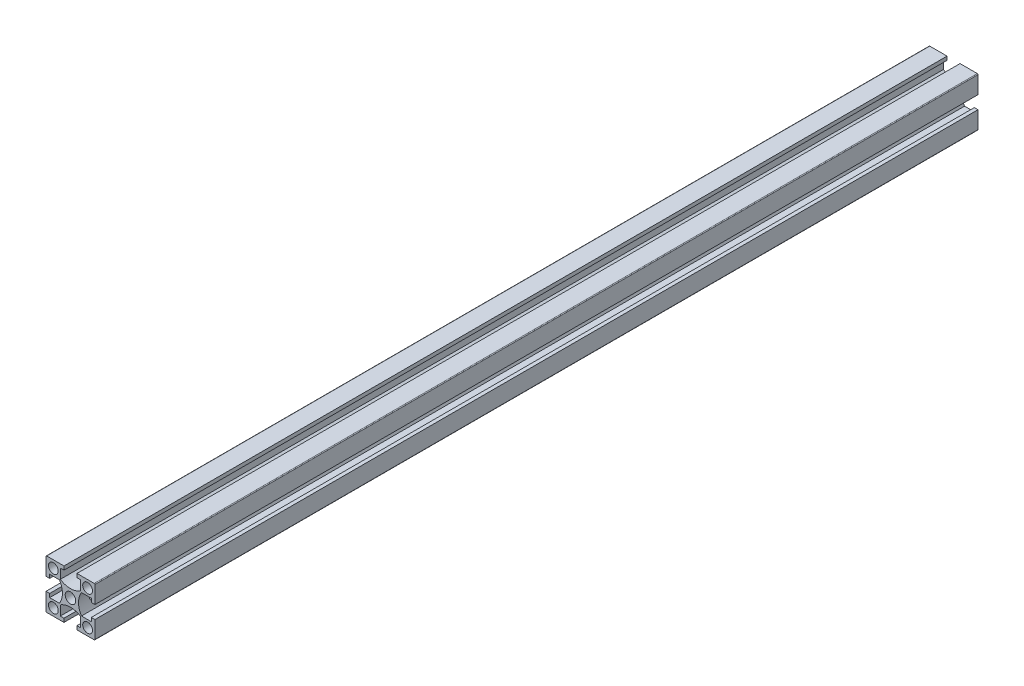
SolidWorks part; units mm, degrees
material "3.0255 (EN-AW 1350A)"
ref_plane "정면" through (0, 0, 0) normal (0, 0, 1) x (1, 0, 0)
ref_plane "윗면" through (0, 0, 0) normal (0, 1, 0) x (1, 0, 0)
ref_plane "우측면" through (0, 0, 0) normal (1, 0, 0) x (0, 0, -1)
sketch "스케치1" plane through (0, 0, 0) normal (0, 0, 1) x (1, 0, 0)
  line L0 (0, 32.0265) -> (0, -31.6588) construction
  line L1 (-10, 10) -> (-10, -10)
  line L2 (-10, 10) -> (10, 10)
  line L3 (-10, 2.65) -> (-8.5, 2.65)
  line L4 (13.6618, 0) -> (-11.6993, 0) construction
  line L5 (-8.5, 2.65) -> (-8.5, 4.15)
  line L6 (-8.5, 4.15) -> (-4.5032, 4.15)
  line L7 (-10, -2.65) -> (-8.5, -2.65)
  line L8 (-8.5, -2.65) -> (-8.5, -4.15)
  line L9 (-8.5, -4.15) -> (-4.5032, -4.15)
  line L10 (-10, -10) -> (10, -10)
  line L11 (10, 10) -> (10, -10)
  circle A0 centre (-7, 7) radius 2
  circle A1 centre (-7, -7) radius 2
  arc A2 (-4.5032, 4.15) -> (-4.5032, -4.15) centre (-11.0587, 0) cw
  circle A3 centre (0, 0) radius 2.15
  circle A4 centre (7, 7) radius 2
  circle A5 centre (7, -7) radius 2
  point P21 (-10, 0)
  point P23 (-3.3, 0)
  point P31 (0, -10)
  point P32 (0, 10)
  dimension "D3" = 4
  dimension "D9" = 6.7
  dimension "D10" = 4.3
  dimension "D11" = 7.7587
  dimension "D1" = 20
  dimension "D2" = 20
  dimension "D4" = 14
  dimension "D5" = 14
  dimension "D6" = 5.3
  dimension "D7" = 8.3
  dimension "D8" = 1.5
extrude "보스-돌출1" add sketch "스케치1" along normal blind 361 contours A0 | A4 | A3 | A5 | A1 | A2 L6 L5 L3 L1 L7 L8 L9 | L2 L11 L10 L1 region at (-6.6069, 0, 0) region at (-7, 7, 0) region at (-7, -7, 0) region at (0, 0, 0) region at (7, 7, 0) region at (7, -7, 0)
extrude "컷-돌출1" cut sketch "스케치1<3>" along normal up to next contours A2 L6 L5 L3 L1 L7 L8 L9 region at (-6.6069, 0, 0)
sketch "스케치1<3>" plane through (0, 0, 0) normal (0, 0, 1) x (1, 0, 0) same geometry as "스케치1"
pattern_circular "원형 패턴1" count 4 over 360 about axis through (0, 0, 361) along (0, 0, -1) of "컷-돌출1" reverse direction yes
fillet "필렛1" radius 0.3 4 edges at (10, -10, 180.5) (-10, -10, 180.5) (-10, 10, 180.5) (10, 10, 180.5)
sketch "스케치4" plane through (0, 10, 0) normal (0, 1, 0) x (1, 0, 0)
  line L0 (-4.15, -361) -> (4.15, -361) construction
  line L1 (2.65, 0) -> (9.7, 0) construction
  line L2 (-9.7, 0) -> (-2.65, 0) construction
  circle A1 centre (0, -56) radius 2.15
  circle A2 centre (0, -108) radius 2.15
  circle A4 centre (0, -351) radius 2.15
  circle A5 centre (0, -271) radius 2.15
  dimension "D1" = 10
  dimension "D2" = 52
  dimension "D3" = 108
  dimension "D4" = 80
extrude "컷-돌출3" cut sketch "스케치4" against normal through all
sketch "스케치6" plane through (-10, 0, 0) normal (-1, 0, 0) x (0, 0, 1)
  line L0 (281, -73) -> (361, 7) construction
  line L1 (361, 10) -> (281, 10)
  line L2 (361, 10) -> (361, 7)
  line L3 (361, 7) -> (281, 7)
  line L4 (281, 10) -> (281, 7)
  line L5 (361, 7) -> (281, 7)
  line L6 (361, 7) -> (361, -73)
  line L7 (361, -73) -> (281, -73)
  line L8 (281, 7) -> (281, -73)
  circle A0 centre (321, -33) radius 47
  circle A1 centre (287.766, -66.234) radius 2.5
  circle A2 centre (287.766, 0.234) radius 2.5
  circle A3 centre (354.234, 0.234) radius 2.5
  circle A4 centre (354.234, -66.234) radius 2.5
  point P20 (321, -33)
  dimension "D4" = 4
  dimension "D5" = 5
  dimension "D1" = 3
  dimension "D2" = 80
  dimension "D3" = 80
extrude "컷-돌출4" cut sketch "스케치6" against normal through all contours A2 | A3
